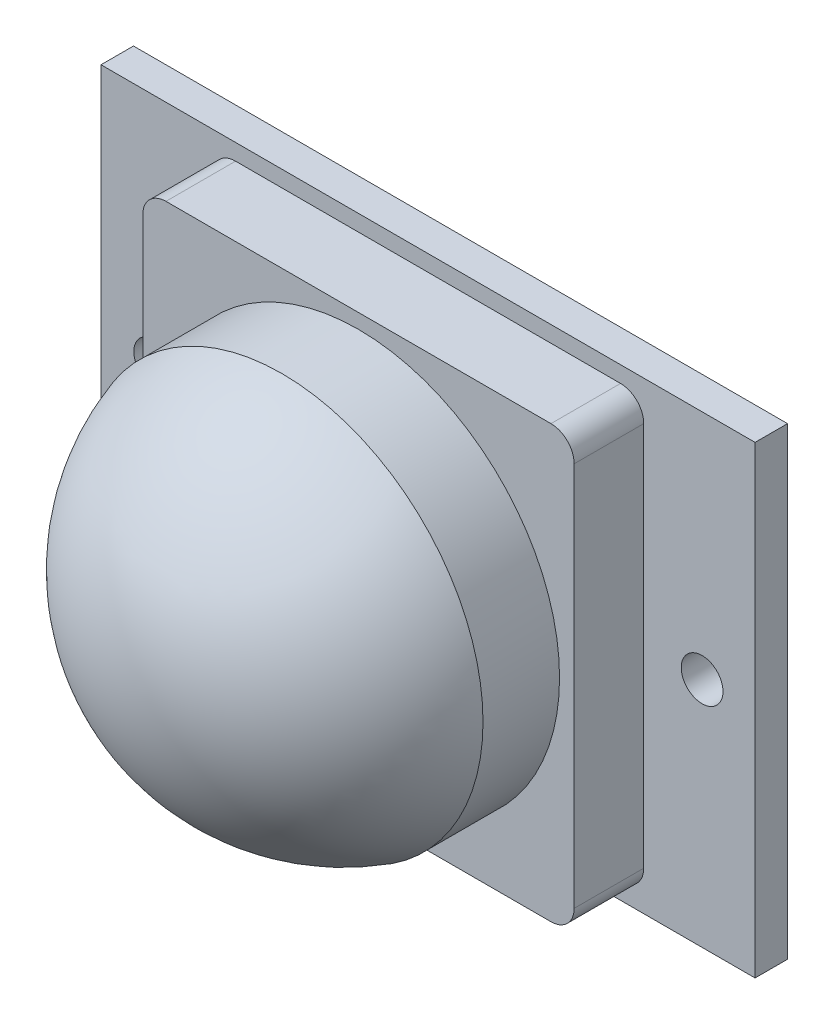
SolidWorks part; units mm, degrees
ref_plane "Front Plane" through (0, 0, 0) normal (0, 0, 1) x (1, 0, 0)
ref_plane "Top Plane" through (0, 0, 0) normal (0, 1, 0) x (1, 0, 0)
ref_plane "Right Plane" through (0, 0, 0) normal (1, 0, 0) x (0, 0, -1)
sketch "Sketch1" plane through (0, 0, 0) normal (0, 0, 1) x (1, 0, 0)
  line L1 (0, 0) -> (35.814, 0)
  line L2 (0, 0) -> (0, 25.4)
  line L3 (0, 25.4) -> (35.814, 25.4)
  line L4 (35.814, 0) -> (35.814, 25.4)
  dimension "D1" = 35.814
  dimension "D2" = 25.4
extrude "Boss-Extrude1" add sketch "Sketch1" along normal blind 1.778
sketch "Sketch2" plane through (0, 0, 1.778) normal (0, 0, 1) x (1, 0, 0)
  line L1 (0, 0) -> (35.814, 0) construction
  line L2 (35.814, 25.4) -> (0, 25.4) construction
  line L3 (35.814, 0) -> (35.814, 25.4) construction
  circle A0 centre (2.942, 12.7) radius 1.143
  circle A1 centre (32.914, 12.7) radius 1.143
  dimension "D1" = 2.286
  dimension "D2" = 2.286
  dimension "D3" = 29.972
  dimension "D4" = 12.7
  dimension "D5" = 12.7
  dimension "D6" = 2.9
extrude "Cut-Extrude1" cut sketch "Sketch2" against normal blind 2.54
sketch "Sketch3" plane through (0, 0, 1.778) normal (0, 0, 1) x (1, 0, 0)
  line L0 (35.814, 25.4) -> (0, 25.4) construction
  line L1 (6.096, 24.511) -> (29.718, 24.511)
  line L2 (6.096, 24.511) -> (6.096, 0.889)
  line L3 (6.096, 0.889) -> (29.718, 0.889)
  line L4 (29.718, 24.511) -> (29.718, 0.889)
  line L5 (35.814, 0) -> (35.814, 25.4) construction
  point P4 (17.907, 24.511)
  point P7 (17.907, 25.4)
  point P8 (29.718, 12.7)
  point P11 (35.814, 12.7)
  dimension "D1" = 23.622
  dimension "D2" = 23.622
  dimension "D3" = 0
  dimension "D4" = 0
extrude "Boss-Extrude3" add sketch "Sketch3" along normal blind 3.81
sketch "Sketch4" plane through (0, 0, 5.588) normal (0, 0, 1) x (1, 0, 0)
  line L0 (35.814, 25.4) -> (0, 25.4) construction
  line L1 (0, 25.4) -> (0, 0) construction
  circle A0 centre (17.907, 12.7) radius 11.0109
  dimension "D1" = 22.0218
  dimension "D2" = 12.7
  dimension "D3" = 17.907
extrude "Boss-Extrude4" add sketch "Sketch4" along normal blind 4.191
dome "Dome3" faces to dome 1 distance 8.128 reverse direction no elliptical dome no face at (28.9179, 12.7, 9.779) parameters "D1"=8.128
fillet "Fillet1" radius 1.27 4 edges at (6.096, 0.889, 3.683) (29.718, 0.889, 3.683) (29.718, 24.511, 3.683) (6.096, 24.511, 3.683)
